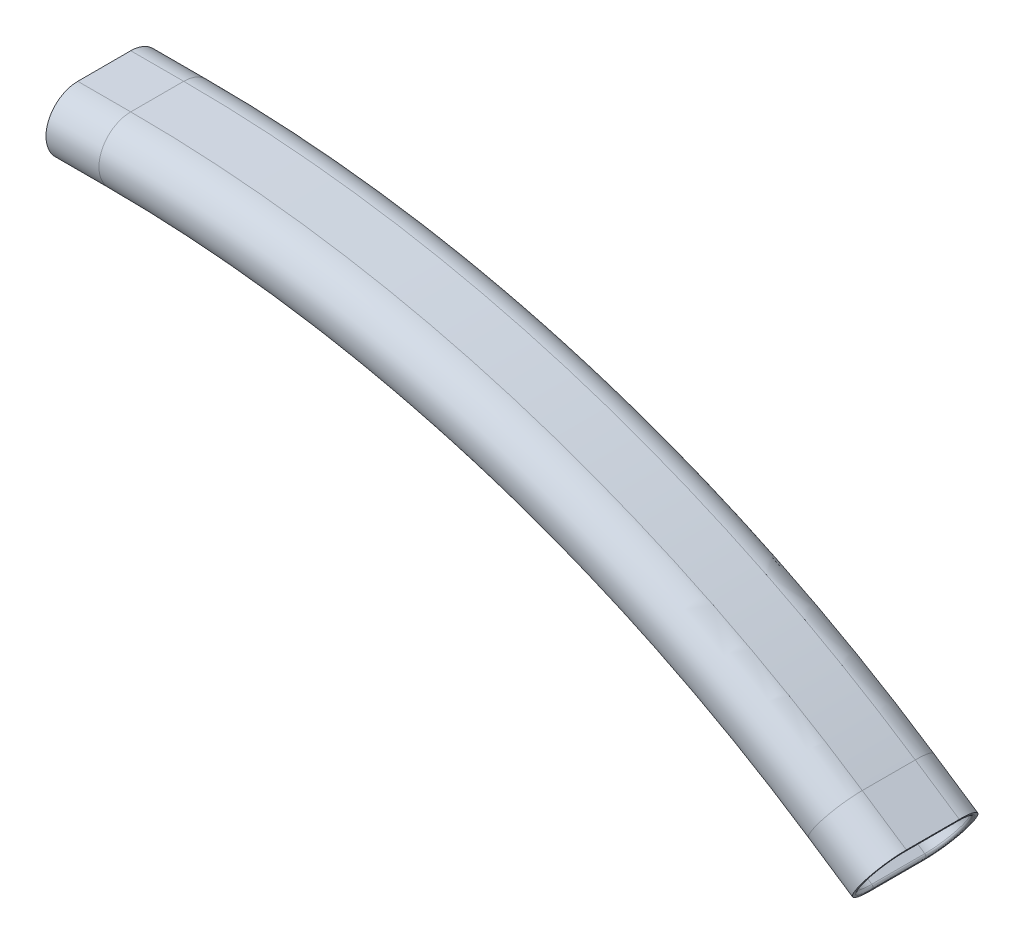
SolidWorks part; units mm, degrees
ref_plane "Front" through (0, 0, 0) normal (0, 0, 1) x (1, 0, 0)
ref_plane "Top" through (0, 0, 0) normal (0, 1, 0) x (1, 0, 0)
ref_plane "Right" through (0, 0, 0) normal (1, 0, 0) x (0, 0, -1)
sketch "Sketch2path" plane through (0, 0, 0) normal (0, 0, 1) x (1, 0, 0)
  line L2 (0, 100) -> (10, 100)
  line L3 (144.7958, 59.1102) -> (153.1105, 53.5545)
  arc A1 (10, 100) -> (144.7958, 59.1102) centre (10, -142.626) cw
  dimension "D1" = 160
  dimension "D3" = 10
  dimension "D4" = 10
  dimension "D5" = 33.75
sketch "Sketch3" plane through (0, 0, 0) normal (1, 0, 0) x (0, 0, -1)
  line L0 (0, 91.8161) -> (0, 108.1839) construction
  line L1 (-5, 100) -> (5, 100) construction
  line L2 (-5, 105) -> (5, 105)
  line L3 (-5, 95) -> (5, 95)
  line L4 (-5, 106) -> (5, 106)
  line L5 (-5, 94) -> (5, 94)
  arc A2 (5, 94) -> (5, 106) centre (5, 100) ccw
  arc A3 (-5, 105) -> (-5, 95) centre (-5, 100) ccw
  arc A4 (5, 95) -> (5, 105) centre (5, 100) ccw
  arc A5 (-5, 106) -> (-5, 94) centre (-5, 100) ccw
  point P11 (0, 100)
  dimension "D1" = 100
  dimension "D4" = 6
  dimension "D5" = 5
sweep "Sweep1" add profiles "Sketch3" path "Sketch2path"
ref_point "Point1"
ref_point "Point2"
ref_axis "Axis1" through (153.1105, 53.5545, 0) along (0, 0, 1)
ref_axis "Axis2" through (0, 100, 0) along (0, 0, 1)
ref_axis "Axis3" through (10, 100, 0) along (-1, 0, 0)
ref_axis "Axis4" through (147.3622, 57.3953, 0) along (0.8315, -0.5556, 0)
ref_plane "Plane1" through (76.9554, -51.4199, 0) normal (0.8315, -0.5556, 0) x (0, 0, -1)
sketch "Sketch4" plane through (76.9554, -51.4199, 0) normal (0.8315, -0.5556, 0) x (0, 0, -1)
  line L1 (4.7631, 126.8425) -> (5.6292, 126.3425)
  line L3 (6.5, 129.5925) -> (5.5, 129.5925)
  arc A0 (5.6292, 126.3425) -> (6.5, 129.5925) centre (0, 129.5925) ccw
  arc A1 (4.7631, 126.8425) -> (5.5, 129.5925) centre (0, 129.5925) ccw
  dimension "D3" = 4.7631
  dimension "D4" = 126.3425
  dimension "D1" = 6.5
  dimension "D2" = 5.5
extrude "Boss-Extrude1" [suppressed] add sketch "Sketch4" against normal blind 5
ref_plane "Plane2" through (5, 0, 0) normal (-1, 0, 0) x (0, 0, 1)
sketch "Sketch5" plane through (5, 0, 0) normal (-1, 0, 0) x (0, 0, 1)
  line L0 (0, 100) -> (8.3914, 100) construction
  line L1 (-4.7631, 102.75) -> (-5.6292, 103.25)
  line L3 (-6.5, 100) -> (-5.5, 100)
  arc A0 (-5.6292, 103.25) -> (-6.5, 100) centre (0, 100) ccw
  arc A1 (-4.7631, 102.75) -> (-5.5, 100) centre (0, 100) ccw
  circle A3 centre (0, 100) radius 7.75 construction
  dimension "D3" = 1
  dimension "D1" = 30
  dimension "D2" = 6.5
extrude "Boss-Extrude2" [suppressed] add sketch "Sketch5" against normal blind 5
ref_plane "Plane3" [suppressed] through (0, 0, 9) normal (0, 0, 1) x (1, 0, 0)
sketch "Sketch6" [suppressed] plane through (0, 0, 9) normal (0, 0, 1) x (1, 0, 0)
  line L0 (0, 100) -> (0, 99.5)
  line L1 (0, 109) -> (0, 91) construction
  line L2 (0, 99.5) -> (3, 99.5)
  line L3 (3, 99.5) -> (3, 100)
  line L4 (10, 100) -> (-12.0198, 100) construction
  line L5 (3, 100) -> (0, 100)
  dimension "D1" = 0.5
  dimension "D2" = 3
revolve "Cut-Revolve1" [suppressed] cut sketch "Sketch6" angle 360 about L5
sketch "Sketch7" [suppressed] plane through (0, 0, 9) normal (0, 0, 1) x (1, 0, 0)
  line L0 (153.1105, 53.5545) -> (150.616, 55.2212)
  line L1 (148.1103, 46.0712) -> (158.1106, 61.0377) construction
  line L2 (147.3622, 57.3953) -> (165.8801, 45.0221) construction
  line L3 (150.616, 55.2212) -> (150.3383, 54.8054)
  line L4 (150.3383, 54.8054) -> (152.8327, 53.1387)
  line L5 (152.8327, 53.1387) -> (153.1105, 53.5545)
  dimension "D1" = 0.5
  dimension "D2" = 3
revolve "Cut-Revolve2" [suppressed] cut sketch "Sketch7" angle 360 about L0
fillet "Fillet1" radius 0.5 8 edges at (0, 100, 10) (0, 105, 0) (0, 100, -10) (153.1105, 53.5545, 10) (155.8883, 57.7118, 0) (153.1105, 53.5545, -10) (0, 95, 0) (150.3326, 49.3971, 0)
